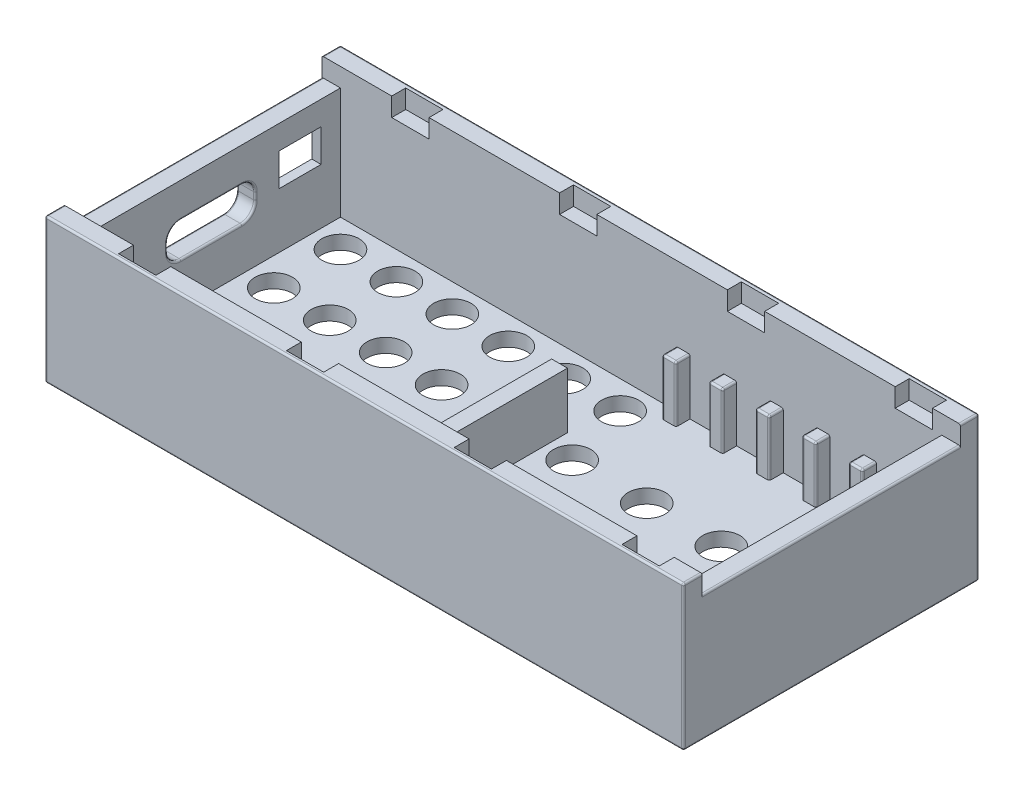
SolidWorks part; units mm, degrees
material "PLA"
ref_plane "前视基准面" through (0, 0, 0) normal (0, 0, 1) x (1, 0, 0)
ref_plane "上视基准面" through (0, 0, 0) normal (0, 1, 0) x (1, 0, 0)
ref_plane "右视基准面" through (0, 0, 0) normal (1, 0, 0) x (0, 0, -1)
sketch "草图1" plane through (0, 0, 0) normal (0, 0, 1) x (1, 0, 0)
  line L0 (0, 0) -> (68.5, 0)
  line L1 (68.5, 0) -> (68.5, 13.5)
  line L2 (68.5, 13.5) -> (66.5, 13.5)
  line L3 (66.5, 13.5) -> (66.5, 1.5)
  line L4 (66.5, 1.5) -> (2, 1.5)
  line L5 (2, 1.5) -> (2, 13.5)
  line L6 (2, 13.5) -> (0, 13.5)
  line L7 (0, 13.5) -> (0, 0)
  dimension "D1" = 64.5
  dimension "D3" = 2
  dimension "D4" = 1.5
  dimension "D6" = 12
extrude "凸台-拉伸1" add sketch "草图1" along normal blind 31.7
sketch "草图3" plane through (0, 1.5, 0) normal (0, 1, 0) x (1, 0, 0)
  line L0 (2, -31.7) -> (66.5, -31.7)
  line L1 (66.5, -31.7) -> (66.5, -29.7)
  line L2 (66.5, -31.7) -> (66.5, 0) construction
  line L3 (66.5, -29.7) -> (2, -29.7)
  line L4 (2, -31.7) -> (2, 0) construction
  line L5 (2, -29.7) -> (2, -31.7)
  dimension "D1" = 2
extrude "凸台-拉伸2" add sketch "草图3" along normal through all
sketch "草图4" plane through (0, 1.5, 0) normal (0, 1, 0) x (1, 0, 0)
  line L0 (2, 0) -> (66.5, 0)
  line L1 (66.5, -29.7) -> (66.5, 0) construction
  line L2 (66.5, -29.7) -> (66.5, 0) construction
  line L3 (66.5, 0) -> (66.5, -2)
  line L4 (66.5, -2) -> (2, -2)
  line L5 (2, -29.7) -> (2, 0) construction
  line L6 (2, -2) -> (2, 0)
  dimension "D1" = 2
extrude "凸台-拉伸3" add sketch "草图4" along normal through all
sketch "草图5" plane through (0, 1.5, 0) normal (0, 1, 0) x (1, 0, 0)
  line L0 (33.6, -6.415) -> (33.6, -25.7073) construction
  line L2 (23.9227, -15.85) -> (46.7103, -15.85) construction
  line L3 (2, -2) -> (66.5, -2) construction
  line L4 (66.5, -29.7) -> (2, -29.7) construction
  line L5 (34.2, -9.85) -> (33, -9.85)
  line L6 (33, -9.85) -> (33, -21.85)
  line L7 (34.2, -9.85) -> (34.2, -21.85)
  line L8 (34.2, -21.85) -> (33, -21.85)
  line L9 (2, -29.7) -> (2, -2) construction
  point P14 (33.6, -9.85)
  point P16 (34.2, -15.85)
  point P17 (33, -15.85)
  dimension "D1" = 1.2
  dimension "D2" = 31.6
  dimension "D3" = 12
extrude "凸台-拉伸4" add sketch "草图5" along normal blind 6 contours L6 L8 L7 L5
sketch "草图10" plane through (0, 0, 0) normal (-1, 0, 0) x (0, 0, 1)
  line L0 (5.075, 9.1862) -> (7.575, 9.1862) construction
  line L1 (5.075, 8.1862) -> (5.075, 10.1862) construction
  line L2 (7.575, 10.1862) -> (7.575, 8.1862) construction
  line L3 (6.325, 8.1862) -> (6.325, 10.1862) construction
  line L4 (7.575, 8.1862) -> (5.075, 8.1862) construction
  line L5 (5.075, 10.1862) -> (7.575, 10.1862) construction
  line L7 (8.575, 7.4362) -> (4.075, 7.4362)
  line L8 (8.575, 7.4362) -> (8.575, 10.9362)
  line L9 (8.575, 10.9362) -> (4.075, 10.9362)
  line L10 (4.075, 7.4362) -> (4.075, 10.9362)
  line L11 (8.575, 7.4362) -> (4.075, 10.9362) construction
  line L12 (8.575, 10.9362) -> (4.075, 7.4362) construction
  point P12 (6.325, 9.1862)
  dimension "D1" = 3.5
  dimension "D2" = 4.5
extrude "切除-拉伸3" cut sketch "草图10" against normal up to next
sketch "草图11" plane through (0, 0, 0) normal (-1, 0, 0) x (0, 0, 1)
  line L14 (11.13, 8.3362) -> (11.13, 7.5762)
  line L15 (12.58, 6.1262) -> (19.12, 6.1262)
  line L16 (20.57, 7.5762) -> (20.57, 8.3362)
  line L17 (19.12, 9.7862) -> (12.58, 9.7862)
  line L18 (11.13, 8.3362) -> (11.13, 7.5762)
  line L19 (12.58, 6.1262) -> (19.12, 6.1262)
  line L20 (20.57, 7.5762) -> (20.57, 8.3362)
  line L21 (19.12, 9.7862) -> (12.58, 9.7862)
  arc A8 (11.13, 7.5762) -> (12.58, 6.1262) centre (12.58, 7.5762) ccw
  arc A9 (19.12, 6.1262) -> (20.57, 7.5762) centre (19.12, 7.5762) ccw
  arc A10 (20.57, 8.3362) -> (19.12, 9.7862) centre (19.12, 8.3362) ccw
  arc A11 (12.58, 9.7862) -> (11.13, 8.3362) centre (12.58, 8.3362) ccw
  arc A12 (11.13, 7.5762) -> (12.58, 6.1262) centre (12.58, 7.5762) ccw
  arc A13 (19.12, 6.1262) -> (20.57, 7.5762) centre (19.12, 7.5762) ccw
  arc A14 (20.57, 8.3362) -> (19.12, 9.7862) centre (19.12, 8.3362) ccw
  arc A15 (12.58, 9.7862) -> (11.13, 8.3362) centre (12.58, 8.3362) ccw
  dimension "D1" = 0.3
extrude "切除-拉伸4" cut sketch "草图11" against normal up to next
sketch "草图14" plane through (0, 0, 2) normal (0, 0, 1) x (1, 0, 0)
  line L0 (64.4954, 1.5) -> (64.4954, 7.5)
  line L1 (2, 1.5) -> (66.5, 1.5) construction
  line L2 (64.4954, 7.5) -> (62.9954, 7.5)
  line L3 (62.9954, 7.5) -> (62.9954, 1.5)
  line L4 (62.9954, 1.5) -> (64.4954, 1.5)
  line L5 (66.5, 13.5) -> (66.5, 1.5) construction
  line L6 (62.1133, 1.5) -> (62.1133, 7.9181) construction
  line L7 (57.9954, 7.5) -> (57.9954, 1.5)
  line L8 (59.4954, 7.5) -> (57.9954, 7.5)
  line L9 (59.4954, 1.5) -> (59.4954, 7.5)
  line L10 (57.9954, 1.5) -> (59.4954, 1.5)
  line L11 (52.9954, 7.5) -> (52.9954, 1.5)
  line L12 (54.4954, 7.5) -> (52.9954, 7.5)
  line L13 (54.4954, 1.5) -> (54.4954, 7.5)
  line L14 (52.9954, 1.5) -> (54.4954, 1.5)
  line L15 (47.9954, 7.5) -> (47.9954, 1.5)
  line L16 (49.4954, 7.5) -> (47.9954, 7.5)
  line L17 (49.4954, 1.5) -> (49.4954, 7.5)
  line L18 (47.9954, 1.5) -> (49.4954, 1.5)
  line L19 (42.9954, 7.5) -> (42.9954, 1.5)
  line L20 (44.4954, 7.5) -> (42.9954, 7.5)
  line L21 (44.4954, 1.5) -> (44.4954, 7.5)
  line L22 (42.9954, 1.5) -> (44.4954, 1.5)
  line L23 (37.9954, 7.5) -> (37.9954, 1.5)
  line L24 (39.4954, 7.5) -> (37.9954, 7.5)
  line L25 (39.4954, 1.5) -> (39.4954, 7.5)
  line L26 (37.9954, 1.5) -> (39.4954, 1.5)
  line L27 (62.9954, 7.5) -> (57.9954, 7.5) construction
  dimension "D1" = 1.5
  dimension "D2" = 6
  dimension "D3" = 2.0046
  dimension "D4" = 0.8821
  dimension "D6" = 5
  dimension "D5" = 6
extrude "凸台-拉伸7" add sketch "草图14" along normal blind 1.5
fillet "圆角5" radius 0.2 18 edges at (64.4954, 4.5, 3.5) (63.7454, 7.5, 3.5) (62.9954, 4.5, 3.5) (59.4954, 4.5, 3.5) (58.7454, 7.5, 3.5) (57.9954, 4.5, 3.5) (54.4954, 4.5, 3.5) (53.7454, 7.5, 3.5) (52.9954, 4.5, 3.5) (49.4954, 4.5, 3.5) (48.7454, 7.5, 3.5) (47.9954, 4.5, 3.5) (44.4954, 4.5, 3.5) (43.7454, 7.5, 3.5) (42.9954, 4.5, 3.5) (39.4954, 4.5, 3.5) (38.7454, 7.5, 3.5) (37.9954, 4.5, 3.5)
fillet "圆角6" radius 0.2 24 edges at (64.4368, 7.4414, 3.4414) (63.0539, 7.4414, 3.4414) (58.0539, 7.4414, 3.4414) (59.4368, 7.4414, 3.4414) (54.4368, 7.4414, 3.4414) (49.4368, 7.4414, 3.4414) (44.4368, 7.4414, 3.4414) (39.4368, 7.4414, 3.4414) (53.0539, 7.4414, 3.4414) (48.0539, 7.4414, 3.4414) (43.0539, 7.4414, 3.4414) (38.0539, 7.4414, 3.4414) (64.4954, 7.5, 2.65) (62.9954, 7.5, 2.65) (57.9954, 7.5, 2.65) (59.4954, 7.5, 2.65) (54.4954, 7.5, 2.65) (49.4954, 7.5, 2.65) (44.4954, 7.5, 2.65) (39.4954, 7.5, 2.65) (52.9954, 7.5, 2.65) (47.9954, 7.5, 2.65) (42.9954, 7.5, 2.65) (37.9954, 7.5, 2.65)
sketch "草图15" plane through (0, 0, 29.7) normal (0, 0, -1) x (-1, 0, 0)
  line L0 (-66.5, 1.5) -> (-2, 1.5) construction
  line L1 (-64.5, 1.5) -> (-63, 1.5)
  line L2 (-64.5, 1.5) -> (-64.5, 7.5)
  line L3 (-64.5, 7.5) -> (-63, 7.5)
  line L4 (-63, 1.5) -> (-63, 7.5)
  line L5 (-66.5, 13.5) -> (-66.5, 1.5) construction
  line L6 (-59.5, 1.5) -> (-59.5, 7.5)
  line L7 (-59.5, 7.5) -> (-58, 7.5)
  line L8 (-58, 1.5) -> (-58, 7.5)
  line L9 (-59.5, 1.5) -> (-58, 1.5)
  line L10 (-54.5, 1.5) -> (-54.5, 7.5)
  line L11 (-54.5, 7.5) -> (-53, 7.5)
  line L12 (-53, 1.5) -> (-53, 7.5)
  line L13 (-54.5, 1.5) -> (-53, 1.5)
  line L14 (-49.5, 1.5) -> (-49.5, 7.5)
  line L15 (-49.5, 7.5) -> (-48, 7.5)
  line L16 (-48, 1.5) -> (-48, 7.5)
  line L17 (-49.5, 1.5) -> (-48, 1.5)
  line L18 (-44.5, 1.5) -> (-44.5, 7.5)
  line L19 (-44.5, 7.5) -> (-43, 7.5)
  line L20 (-43, 1.5) -> (-43, 7.5)
  line L21 (-44.5, 1.5) -> (-43, 1.5)
  line L22 (-39.5, 1.5) -> (-39.5, 7.5)
  line L23 (-39.5, 7.5) -> (-38, 7.5)
  line L24 (-38, 1.5) -> (-38, 7.5)
  line L25 (-39.5, 1.5) -> (-38, 1.5)
  line L26 (-64.5, 1.5) -> (-59.5, 1.5) construction
  dimension "D1" = 2
  dimension "D2" = 1.5
  dimension "D3" = 6
  dimension "D5" = 5
  dimension "D4" = 6
extrude "凸台-拉伸8" add sketch "草图15" along normal blind 1.5
fillet "圆角7" radius 0.2 30 edges at (38, 7.5, 28.95) (38.75, 7.5, 28.2) (38, 4.5, 28.2) (39.5, 4.5, 28.2) (39.5, 7.5, 28.95) (43, 4.5, 28.2) (44.5, 4.5, 28.2) (43, 7.5, 28.95) (43.75, 7.5, 28.2) (44.5, 7.5, 28.95) (48, 7.5, 28.95) (48, 4.5, 28.2) (48.75, 7.5, 28.2) (49.5, 4.5, 28.2) (49.5, 7.5, 28.95) (53, 7.5, 28.95) (53.75, 7.5, 28.2) (53, 4.5, 28.2) (54.5, 4.5, 28.2) (54.5, 7.5, 28.95) (59.5, 7.5, 28.95) (58, 7.5, 28.95) (58.75, 7.5, 28.2) (58, 4.5, 28.2) (59.5, 4.5, 28.2) (64.5, 4.5, 28.2) (63, 4.5, 28.2) (63, 7.5, 28.95) (63.75, 7.5, 28.2) (64.5, 7.5, 28.95)
sketch "草图16" plane through (0, 0, 0) normal (-1, 0, 0) x (0, 0, 1)
  line L0 (0, 13.5) -> (0, 15.5)
  line L1 (0, 15.5) -> (2, 15.5)
  line L2 (2, 15.5) -> (2, 13.5)
  line L3 (31.7, 13.5) -> (0, 13.5) construction
  line L4 (2, 13.5) -> (0, 13.5)
  line L5 (15.85, 0) -> (15.85, 20.1555) construction
  line L6 (31.7, 0) -> (0, 0) construction
  line L7 (29.7, 13.5) -> (31.7, 13.5)
  line L8 (29.7, 15.5) -> (29.7, 13.5)
  line L9 (31.7, 15.5) -> (29.7, 15.5)
  line L10 (31.7, 13.5) -> (31.7, 15.5)
  dimension "D1" = 2
  dimension "D2" = 2
extrude "凸台-拉伸9" add sketch "草图16" against normal through all
fillet "圆角8" radius 0.2 8 edges at (0, 6.5509, 20.1453) (0, 6.1262, 15.85) (0, 6.5509, 11.5547) (0, 7.9562, 11.13) (0, 9.3615, 11.5547) (0, 9.7862, 15.85) (0, 9.3615, 20.1453) (0, 7.9562, 20.57)
fillet "圆角9" radius 0.2 4 edges at (68.5, 13.5, 15.85) (0, 13.5, 15.85) (34.25, 15.5, 0) (34.25, 15.5, 31.7)
fillet "圆角10" radius 0.2 16 edges at (68.5, 15.5, 1.1) (68.5, 15.4414, 0.0586) (68.5, 15.5, 30.6) (68.5, 15.4414, 31.6414) (0, 15.5, 30.6) (0, 15.4414, 31.6414) (0, 15.5, 1.1) (0, 15.4414, 0.0586) (34.25, 0, 0) (68.5, 0, 15.85) (68.5, 7.65, 0) (68.5, 7.65, 31.7) (34.25, 0, 31.7) (0, 7.65, 31.7) (0, 0, 15.85) (0, 7.65, 0)
fillet "圆角11" radius 0.2 8 edges at (2, 6.5509, 20.1453) (2, 7.9562, 20.57) (2, 9.3615, 20.1453) (2, 9.7862, 15.85) (2, 9.3615, 11.5547) (2, 7.9562, 11.13) (2, 6.5509, 11.5547) (2, 6.1262, 15.85)
sketch "草图17" plane through (0, 0, 0) normal (-1, 0, 0) x (0, 0, 1)
  line L8 (9.575, 6.4362) -> (9.575, 11.9362)
  line L9 (3.075, 6.4362) -> (9.575, 6.4362)
  line L10 (3.075, 11.9362) -> (3.075, 6.4362)
  line L11 (9.575, 11.9362) -> (3.075, 11.9362)
  line L12 (9.575, 6.4362) -> (9.575, 11.9362)
  line L13 (3.075, 6.4362) -> (9.575, 6.4362)
  line L14 (3.075, 11.9362) -> (3.075, 6.4362)
  line L15 (9.575, 11.9362) -> (3.075, 11.9362)
  dimension "D1" = 1
extrude "切除-拉伸5" cut sketch "草图17" against normal blind 1
chamfer "倒角1" distance 0.5 angle 45 4 edges at (0, 9.1862, 9.575) (0, 11.9362, 6.325) (0, 9.1862, 3.075) (0, 6.4362, 6.325)
ref_plane "基准面1" through (0, 0, 15.85) normal (0, 0, -1) x (-1, 0, 0)
sketch "草图19" plane through (0, 15.5, 0) normal (0, 1, 0) x (1, 0, 0)
  line L0 (68.3, -2) -> (0.2, -2) construction
  line L1 (65.5, -2) -> (61.5, -2)
  line L2 (65.5, -2) -> (65.5, -0.5)
  line L3 (65.5, -0.5) -> (61.5, -0.5)
  line L4 (61.5, -2) -> (61.5, -0.5)
  line L5 (68.5, -0.2) -> (68.5, -2) construction
  line L6 (47.5, -2) -> (47.5, -0.5)
  line L7 (47.5, -2) -> (43.5, -2)
  line L8 (43.5, -2) -> (43.5, -0.5)
  line L9 (47.5, -0.5) -> (43.5, -0.5)
  line L10 (29.5, -2) -> (29.5, -0.5)
  line L11 (29.5, -2) -> (25.5, -2)
  line L12 (25.5, -2) -> (25.5, -0.5)
  line L13 (29.5, -0.5) -> (25.5, -0.5)
  line L14 (11.5, -2) -> (11.5, -0.5)
  line L15 (11.5, -2) -> (7.5, -2)
  line L16 (7.5, -2) -> (7.5, -0.5)
  line L17 (11.5, -0.5) -> (7.5, -0.5)
  line L18 (65.5, -2) -> (47.5, -2) construction
  dimension "D1" = 3
  dimension "D2" = 1.5
  dimension "D3" = 4
  dimension "D5" = 18
  dimension "D4" = 4
extrude "切除-拉伸6" cut sketch "草图19" against normal blind 2
sketch "草图21" plane through (0, 0, 29.7) normal (0, 0, -1) x (-1, 0, 0)
  line L0 (-43.5, 15.5) -> (-47.5, 15.5)
  line L1 (-47.5, 15.5) -> (-47.5, 13.5)
  line L2 (-47.5, 13.5) -> (-43.5, 13.5)
  line L3 (-43.5, 13.5) -> (-43.5, 15.5)
  line L4 (-61.5, 15.5) -> (-65.5, 15.5)
  line L5 (-61.5, 13.5) -> (-61.5, 15.5)
  line L6 (-65.5, 13.5) -> (-61.5, 13.5)
  line L7 (-65.5, 15.5) -> (-65.5, 13.5)
  line L8 (-61.5, 15.5) -> (-65.5, 15.5)
  line L9 (-61.5, 13.5) -> (-61.5, 15.5)
  line L10 (-65.5, 13.5) -> (-61.5, 13.5)
  line L11 (-65.5, 15.5) -> (-65.5, 13.5)
  line L12 (-25.5, 15.5) -> (-29.5, 15.5)
  line L13 (-29.5, 15.5) -> (-29.5, 13.5)
  line L14 (-29.5, 13.5) -> (-25.5, 13.5)
  line L15 (-25.5, 13.5) -> (-25.5, 15.5)
  line L16 (-7.5, 15.5) -> (-11.5, 15.5)
  line L17 (-11.5, 15.5) -> (-11.5, 13.5)
  line L18 (-11.5, 13.5) -> (-7.5, 13.5)
  line L19 (-7.5, 13.5) -> (-7.5, 15.5)
  line L20 (-61.5, 15.5) -> (-43.5, 15.5) construction
  dimension "D3" = 18
  dimension "D1" = 0
  dimension "D2" = 4
extrude "切除-拉伸8" cut sketch "草图21" against normal blind 1.6
sketch "草图22" plane through (33, 0, 0) normal (-1, 0, 0) x (0, 0, 1)
  line L0 (9.85, 7.5) -> (21.85, 7.5) construction
  line L1 (9.85, 7.5) -> (21.85, 7.5)
  line L2 (9.85, 7.5) -> (9.85, 6.5)
  line L3 (9.85, 6.5) -> (21.85, 6.5)
  line L4 (21.85, 7.5) -> (21.85, 6.5)
  line L5 (9.85, 7.5) -> (9.85, 1.5) construction
  line L6 (21.85, 7.5) -> (21.85, 1.5) construction
  dimension "D1" = 1
extrude "凸台-拉伸10" add sketch "草图22" along normal blind 0.5
sketch "草图23" plane through (0, 1.5, 0) normal (0, 1, 0) x (1, 0, 0)
  line L1 (5, -12.15) -> (11, -12.15) construction
  line L2 (5, -26.45) -> (11, -26.45) construction
  line L3 (29, -12.15) -> (37, -12.15) construction
  line L4 (29, -19.3) -> (37, -19.3) construction
  circle A0 centre (5, -5) radius 2
  circle A1 centre (11, -5) radius 2
  circle A2 centre (17, -5) radius 2
  circle A3 centre (23, -5) radius 2
  circle A4 centre (29, -5) radius 2
  circle A5 centre (35, -5) radius 2
  circle A6 centre (5, -12.15) radius 2
  circle A7 centre (5, -19.3) radius 2
  circle A8 centre (5, -26.45) radius 2
  circle A9 centre (11, -12.15) radius 2
  circle A10 centre (11, -19.3) radius 2
  circle A11 centre (17, -12.15) radius 2
  circle A12 centre (17, -19.3) radius 2
  circle A13 centre (23, -12.15) radius 2
  circle A14 centre (23, -19.3) radius 2
  circle A15 centre (29, -12.15) radius 2
  circle A16 centre (29, -19.3) radius 2
  circle A17 centre (11, -26.45) radius 2
  circle A18 centre (17, -26.45) radius 2
  circle A19 centre (23, -26.45) radius 2
  circle A20 centre (29, -26.45) radius 2
  circle A21 centre (35, -26.45) radius 2
  circle A22 centre (37, -12.15) radius 2
  circle A23 centre (45, -12.15) radius 2
  circle A24 centre (53, -12.15) radius 2
  circle A25 centre (61, -12.15) radius 2
  circle A26 centre (37, -19.3) radius 2
  circle A27 centre (45, -19.3) radius 2
  circle A28 centre (53, -19.3) radius 2
  circle A29 centre (61, -19.3) radius 2
  dimension "D1" = 4
  dimension "D3" = 5
  dimension "D8" = 5
  dimension "D2" = 5
  dimension "D5" = 6
  dimension "D7" = 7.15
  dimension "D9" = 6
  dimension "D11" = 6
  dimension "D13" = 8
  dimension "D15" = 8
  dimension "D4" = 6
  dimension "D6" = 4
  dimension "D10" = 6
  dimension "D12" = 5
  dimension "D14" = 5
extrude "切除-拉伸9" cut sketch "草图23" against normal up to next (1.5 mm away)
